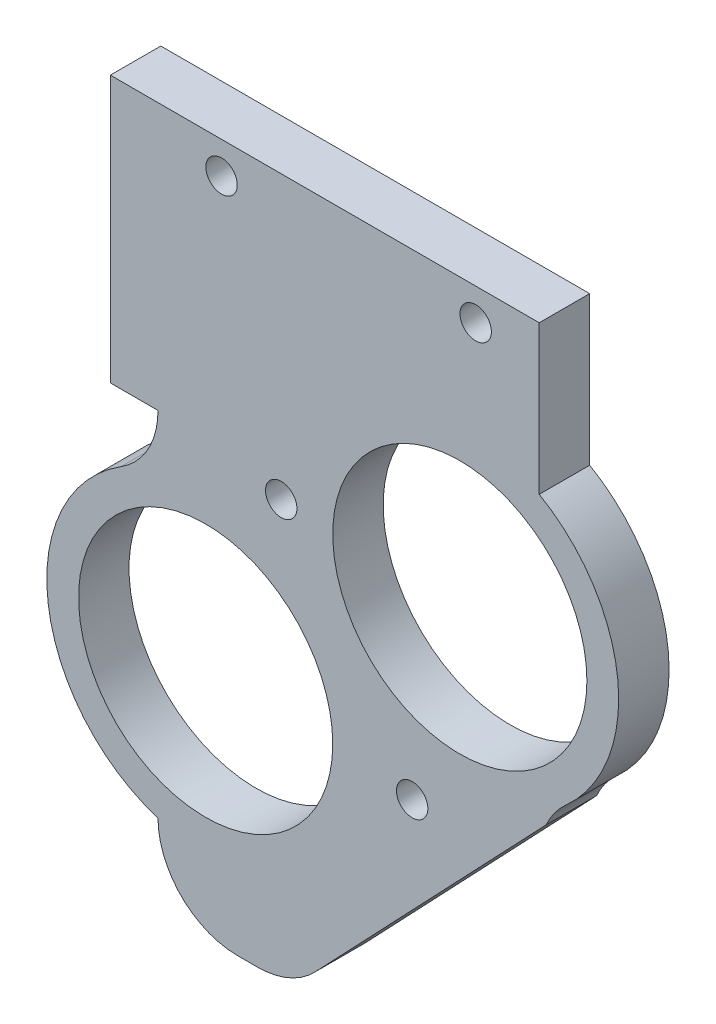
SolidWorks part; units mm, degrees
ref_plane "Front Plane" through (0, 0, 0) normal (0, 0, 1) x (1, 0, 0)
ref_plane "Top Plane" through (0, 0, 0) normal (0, 1, 0) x (1, 0, 0)
ref_plane "Right Plane" through (0, 0, 0) normal (1, 0, 0) x (0, 0, -1)
sketch "Sketch1" plane through (0, 0, 0) normal (0, 0, 1) x (1, 0, 0)
  line L0 (-8.0593, 14.2227) -> (39.9407, 14.2227) construction
  line L1 (15.7715, -0.4257) -> (39.9407, -0.4257)
  line L3 (-8.0593, 47.5743) -> (17.9823, 47.5743)
  line L4 (39.9407, -0.4257) -> (39.9407, 14.2227)
  line L5 (15.9407, 14.2227) -> (15.9407, 31.5432) construction
  line L6 (15.9407, 31.5432) -> (29.9407, 31.5432) construction
  line L7 (15.9407, 14.2227) -> (15.9407, 8.6332) construction
  line L8 (15.9407, 8.6332) -> (-2.0593, 8.6332) construction
  line L9 (-8.0593, 27.7119) -> (-8.0593, 47.5743)
  line L11 (-2.0593, 8.6332) -> (15.9407, 47.5743) construction
  arc A0 (-8.0593, 27.7119) -> (15.7715, -0.4257) centre (-2.0593, 8.6332) ccw
  circle A1 centre (-2.0593, 8.6332) radius 16
  circle A2 centre (29.9407, 31.5432) radius 16
  arc A3 (39.9407, 14.2227) -> (17.9823, 47.5743) centre (29.9407, 31.5432) ccw
  circle A4 centre (15.9407, 47.5743) radius 7 construction
  circle A5 centre (15.9407, 47.5743) radius 7 construction
  circle A6 centre (15.9407, -0.4257) radius 7 construction
  circle A7 centre (15.9407, -0.4257) radius 7 construction
  dimension "D2" = 32
  dimension "D3" = 32
  dimension "D4" = 34.9
  dimension "D9" = 20
  dimension "D10" = 20
  dimension "D1" = 48
  dimension "D5" = 14
  dimension "D6" = 42.9
  dimension "D7" = 18
  dimension "D8" = 48
  dimension "D11" = 24
extrude "Boss-Extrude1" add sketch "Sketch1" along normal blind 6.35
fillet "Fillet1" radius 10 4 edges at (15.7715, -0.4257, 3.175) (39.9407, 14.2227, 3.175) (17.9823, 47.5743, 3.175) (-8.0593, 27.7119, 3.175)
sketch "Sketch2" plane through (0, 0, 0) normal (0, 0, -1) x (-1, 0, 0)
  line L0 (-39.9407, -0.4257) -> (-39.9407, 9.1825) construction
  line L1 (8.0593, 47.5743) -> (-39.9407, 47.5743)
  line L2 (8.0593, 47.5743) -> (8.0593, 67.5743)
  line L3 (8.0593, 67.5743) -> (-39.9407, 67.5743)
  line L4 (-39.9407, 47.5743) -> (-39.9407, 67.5743)
  line L5 (-15.9407, 47.5743) -> (-15.9407, -0.4257) construction
  line L6 (-21.1088, -0.4257) -> (-39.9407, -0.4257) construction
  line L7 (-15.9407, 23.5743) -> (-12.6358, 23.5743) construction
  line L8 (-39.9407, -0.4257) -> (-39.9407, -20.4257)
  line L9 (8.0593, -20.4257) -> (-39.9407, -20.4257)
  line L10 (8.0593, -6.1992) -> (8.0593, -20.4257)
  line L11 (-11.1292, -0.4257) -> (-39.9407, -0.4257)
  circle A0 centre (2.0593, 8.6332) radius 16 construction
  arc A1 (-11.1292, -0.4257) -> (8.0593, -6.1992) centre (2.0593, 8.6332) ccw
  dimension "D1" = 20
extrude "Boss-Extrude2" add sketch "Sketch2" against normal up to surface (6.35 mm away) up to face at (13.9407, 8.6332, 6.35)
sketch "Sketch3" plane through (0, 0, 0) normal (0, 0, -1) x (-1, 0, 0)
sketch "Sketch4" plane through (-8.0593, 0, 0) normal (-1, 0, 0) x (0, 0, 1)
  line L1 (6.35, 67.5743) -> (0, 67.5743)
  line L2 (6.35, 67.5743) -> (6.35, 34.0103)
  line L3 (6.35, 34.0103) -> (0, 34.0103)
  line L4 (0, 67.5743) -> (0, 34.0103)
extrude "Boss-Extrude3" add sketch "Sketch4" along normal blind 6
sketch "Sketch5" plane through (0, 0, 6.35) normal (0, 0, 1) x (1, 0, 0)
  circle A0 centre (31.9407, 63.5743) radius 1.9763
  circle A1 centre (-0.0593, 63.5743) radius 1.9763
  circle A2 centre (23.9407, 7.5743) radius 1.9763
  circle A3 centre (7.4554, 32.0596) radius 1.9763
extrude "Cut-Extrude1" cut sketch "Sketch5" against normal through all
sketch "Sketch6" plane through (-14.0593, 0, 0) normal (-1, 0, 0) x (0, 0, 1)
  circle A0 centre (2.7478, 62.5612) radius 0.8188
  circle A1 centre (2.7568, 51.3138) radius 0.8188
  circle A2 centre (2.7568, 40.3138) radius 0.8188
extrude "Cut-Extrude2" cut sketch "Sketch6" against normal blind 4
sketch "Sketch7" plane through (0, 0, 0) normal (0, 0, -1) x (-1, 0, 0)
  line L0 (-40.812, 13.265) -> (-6.1406, -23.1855)
  line L1 (-6.1406, -23.1855) -> (-44.1636, -23.1855)
  line L2 (-44.1636, -23.1855) -> (-44.1636, 13.265)
  line L3 (-44.1636, 13.265) -> (-40.812, 13.265)
  arc A0 (-39.9407, 9.1825) -> (-43.2741, 16.636) centre (-49.9407, 9.1825) ccw construction
extrude "Cut-Extrude3" cut sketch "Sketch7" against normal through all
fillet "Fillet2" radius 10 2 edges at (-8.0593, -20.4257, 3.175) (8.7657, -20.4257, 3.175)
